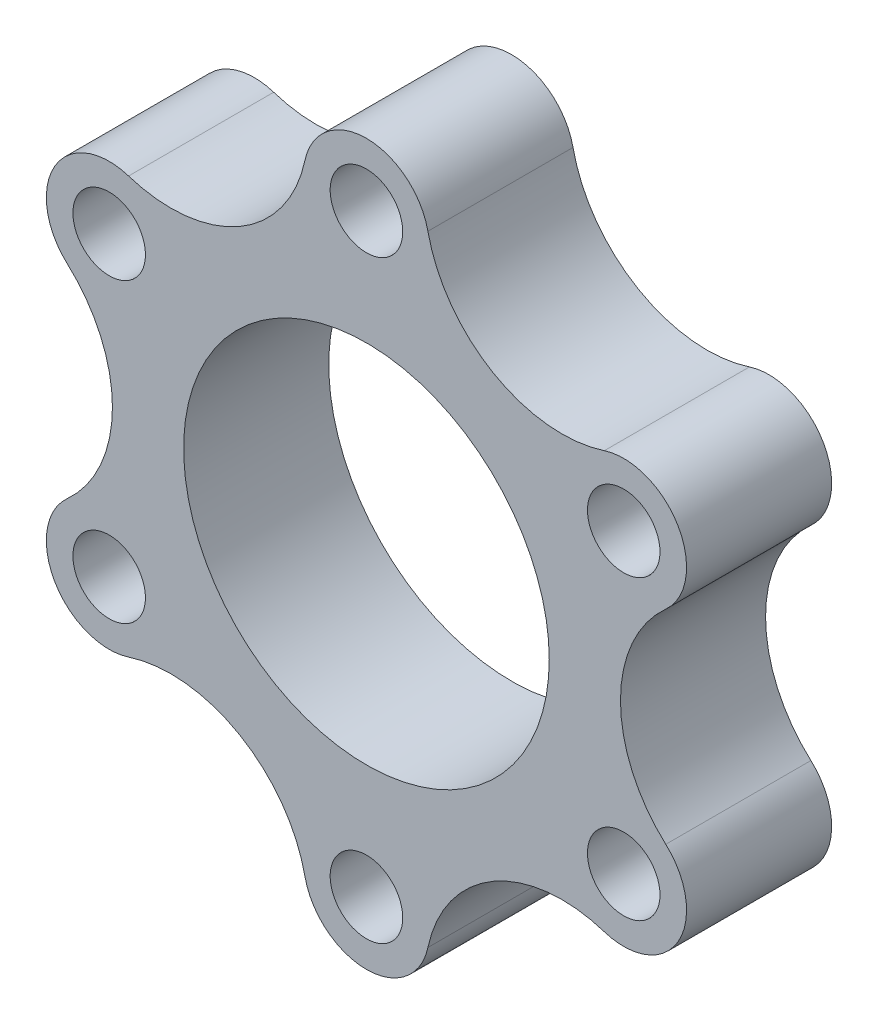
SolidWorks part; units mm, degrees
material "6061-T6 (SS)"
ref_plane "Front Plane" through (0, 0, 0) normal (0, 0, 1) x (1, 0, 0)
ref_plane "Top Plane" through (0, 0, 0) normal (0, 1, 0) x (1, 0, 0)
ref_plane "Right Plane" through (0, 0, 0) normal (1, 0, 0) x (0, 0, -1)
sketch "Sketch1" plane through (0, 0, 0) normal (0, 0, 1) x (1, 0, 0)
  circle A0 centre (0, 0) radius 40 construction
  circle A1 centre (0, 0) radius 35 construction
  circle A2 centre (0, 0) radius 16
  arc A3 (5.3793, 27.1458) -> (-5.3793, 27.1458) centre (0, 26) ccw
  arc A4 (26.1986, 8.9143) -> (20.8193, 18.2315) centre (22.5167, 13) ccw
  arc A5 (20.8193, -18.2315) -> (26.1986, -8.9143) centre (22.5167, -13) ccw
  arc A6 (-5.3793, -27.1458) -> (5.3793, -27.1458) centre (0, -26) ccw
  arc A7 (-26.1986, -8.9143) -> (-20.8193, -18.2315) centre (-22.5167, -13) ccw
  arc A8 (-20.8193, 18.2315) -> (-26.1986, 8.9143) centre (-22.5167, 13) ccw
  arc A9 (-20.8193, 18.2315) -> (-5.3793, 27.1458) centre (-17.116, 29.6458) ccw
  arc A10 (5.3793, 27.1458) -> (20.8193, 18.2315) centre (17.116, 29.6458) ccw
  arc A11 (26.1986, 8.9143) -> (26.1986, -8.9143) centre (34.232, 0) ccw
  arc A12 (20.8193, -18.2315) -> (5.3793, -27.1458) centre (17.116, -29.6458) ccw
  arc A13 (-5.3793, -27.1458) -> (-20.8193, -18.2315) centre (-17.116, -29.6458) ccw
  arc A14 (-26.1986, -8.9143) -> (-26.1986, 8.9143) centre (-34.232, 0) ccw
  arc A15 (-26.1986, 8.9143) -> (-20.8193, 18.2315) centre (-22.5167, 13) ccw construction
  arc A16 (-5.3793, 27.1458) -> (5.3793, 27.1458) centre (0, 26) ccw construction
  arc A17 (20.8193, 18.2315) -> (26.1986, 8.9143) centre (22.5167, 13) ccw construction
  arc A18 (26.1986, -8.9143) -> (20.8193, -18.2315) centre (22.5167, -13) ccw construction
  arc A19 (5.3793, -27.1458) -> (-5.3793, -27.1458) centre (0, -26) ccw construction
  arc A20 (-20.8193, -18.2315) -> (-26.1986, -8.9143) centre (-22.5167, -13) ccw construction
  circle A21 centre (0, 26) radius 3.175
  circle A22 centre (22.5167, 13) radius 3.175
  circle A23 centre (22.5167, -13) radius 3.175
  circle A24 centre (0, -26) radius 3.175
  circle A25 centre (-22.5167, -13) radius 3.175
  circle A26 centre (-22.5167, 13) radius 3.175
  point P19 (0, 0)
  point P38 (0, 0)
  point P44 (0, 0)
  dimension "D1" = 80
  dimension "D2" = 70
  dimension "D3" = 32
  dimension "D4" = 11
  dimension "D7" = 12
  dimension "D9" = 6.35
  dimension "D5" = 26
  dimension "D6" = 6
  dimension "D8" = 6
  dimension "D10" = 6
extrude "Boss-Extrude1" add sketch "Sketch1" along normal mid plane 12.7
equation "\"D9@Sketch1\"=0.25in"
equation "\"D1@Boss-Extrude1\"=0.5in"
